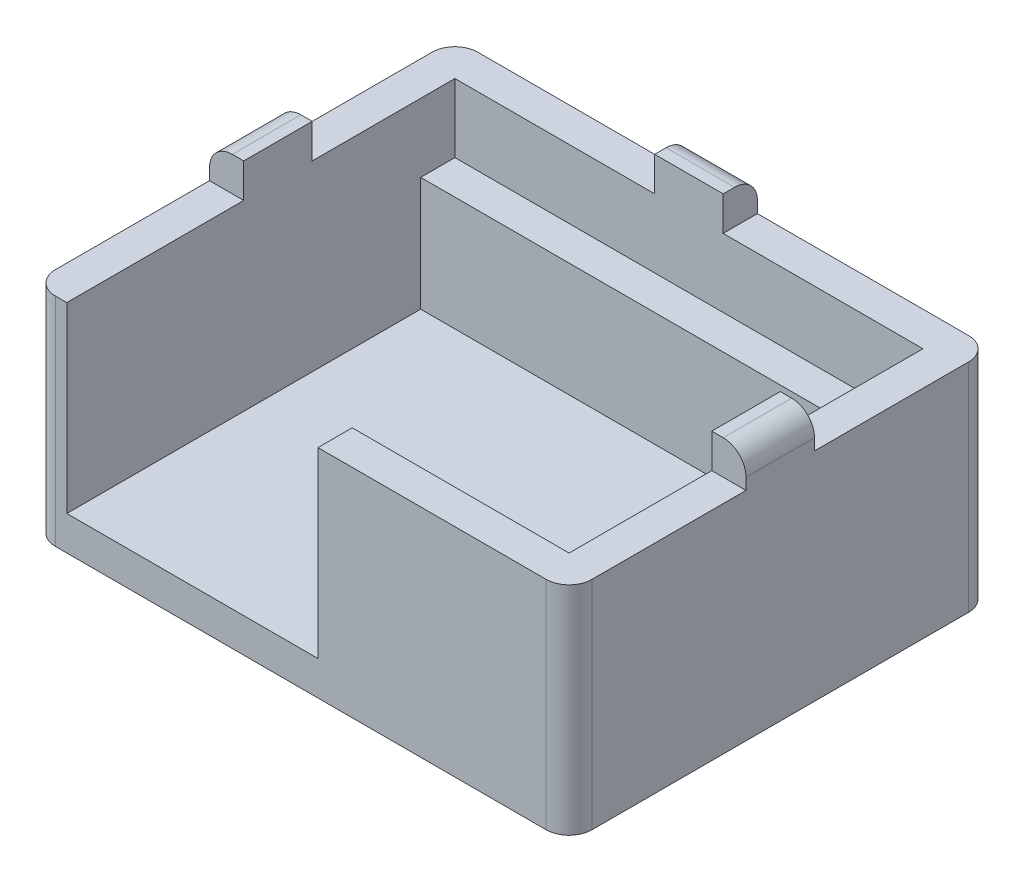
SolidWorks part; units mm, degrees
ref_plane "Front Plane" through (0, 0, 0) normal (0, 0, 1) x (1, 0, 0)
ref_plane "Top Plane" through (0, 0, 0) normal (0, 1, 0) x (1, 0, 0)
ref_plane "Right Plane" through (0, 0, 0) normal (1, 0, 0) x (0, 0, -1)
sketch "Sketch1" plane through (0, 0, 0) normal (0, 1, 0) x (1, 0, 0)
  line L1 (-13.8612, 7.6966) -> (6.6388, 7.6966)
  line L2 (-13.8612, 7.6966) -> (-13.8612, -7.8034)
  line L3 (-13.8612, -7.8034) -> (6.6388, -7.8034)
  line L4 (6.6388, 7.6966) -> (6.6388, -7.8034)
  dimension "D1" = 20.5
  dimension "D2" = 15.5
extrude "Boss-Extrude1" add sketch "Sketch1" along normal blind 8
shell "Shell1" thickness 1.5 removed face at (-3.6112, 8, 0.0534) outward yes
sketch "Sketch2" plane through (0, 0, 0) normal (0, 1, 0) x (1, 0, 0)
  line L1 (8.1388, 9.1966) -> (-15.3612, 9.1966) construction
  line L3 (6.6388, 7.6966) -> (-13.8612, 7.6966) construction
  line L4 (-5.1112, 9.1966) -> (-2.1112, 9.1966)
  line L5 (-5.1112, 9.1966) -> (-5.1112, 7.6966)
  line L6 (-5.1112, 7.6966) -> (-2.1112, 7.6966)
  line L7 (-2.1112, 9.1966) -> (-2.1112, 7.6966)
  line L8 (-15.3612, 9.1966) -> (-15.3612, -9.3034) construction
  line L10 (-13.8612, 7.6966) -> (-13.8612, -7.8034) construction
  line L11 (-15.3612, 1.4466) -> (-13.8612, 1.4466)
  line L12 (-15.3612, 1.4466) -> (-15.3612, -1.5534)
  line L13 (-15.3612, -1.5534) -> (-13.8612, -1.5534)
  line L14 (-13.8612, 1.4466) -> (-13.8612, -1.5534)
  line L15 (8.1388, -9.3034) -> (8.1388, 9.1966) construction
  line L16 (8.1388, 1.4466) -> (6.6388, 1.4466)
  line L17 (8.1388, 1.4466) -> (8.1388, -1.5534)
  line L18 (8.1388, -1.5534) -> (6.6388, -1.5534)
  line L19 (6.6388, 1.4466) -> (6.6388, -1.5534)
  line L20 (6.6388, -7.8034) -> (6.6388, 7.6966) construction
  dimension "D1" = 3
  dimension "D2" = 3
extrude "Boss-Extrude2" add sketch "Sketch2" along normal blind 9.5
sketch "Sketch3" plane through (0, 8, 0) normal (0, 1, 0) x (1, 0, 0)
  line L0 (-15.3612, -9.3034) -> (8.1388, -9.3034) construction
  line L1 (-13.8612, -7.8034) -> (-3.8612, -7.8034)
  line L2 (-13.8612, -7.8034) -> (-13.8612, -9.3034)
  line L3 (-13.8612, -9.3034) -> (-3.8612, -9.3034)
  line L4 (-3.8612, -7.8034) -> (-3.8612, -9.3034)
  dimension "D1" = 10
extrude "Cut-Extrude1" cut sketch "Sketch3" against normal blind 8
sketch "Sketch4" plane through (0, 0, 0) normal (0, 1, 0) x (1, 0, 0)
  line L0 (6.6388, -7.8034) -> (6.6388, 7.6966) construction
  line L1 (-13.8612, 7.6966) -> (6.6388, 7.6966)
  line L2 (-13.8612, 7.6966) -> (-13.8612, 6.1966)
  line L3 (-13.8612, 6.1966) -> (6.6388, 6.1966)
  line L4 (6.6388, 7.6966) -> (6.6388, 6.1966)
  dimension "D1" = 1.5
extrude "Boss-Extrude3" add sketch "Sketch4" along normal blind 5
fillet "Fillet1" radius 1 1 edges at (-15.3612, 9.5, 0.0534)
fillet "Fillet2" radius 1 2 edges at (-3.6112, 9.5, -9.1966) (8.1388, 9.5, 0.0534)
fillet "Fillet3" radius 1 4 edges at (8.1388, 3.25, -9.1966) (8.1388, 3.25, 9.3034) (-15.3612, 3.25, 9.3034) (-15.3612, 3.25, -9.1966)
sketch "Sketch5" plane through (0, 8, 0) normal (0, 1, 0) x (1, 0, 0)
  line L0 (-3.8612, -9.3034) -> (7.1388, -9.3034) construction
  line L1 (-3.8612, -7.8034) -> (-2.8612, -7.8034)
  line L2 (-3.8612, -7.8034) -> (-3.8612, -9.3034)
  line L3 (-3.8612, -9.3034) -> (-2.8612, -9.3034)
  line L4 (-2.8612, -7.8034) -> (-2.8612, -9.3034)
  dimension "D1" = 1
extrude "Cut-Extrude3" cut sketch "Sketch5" against normal blind 8
